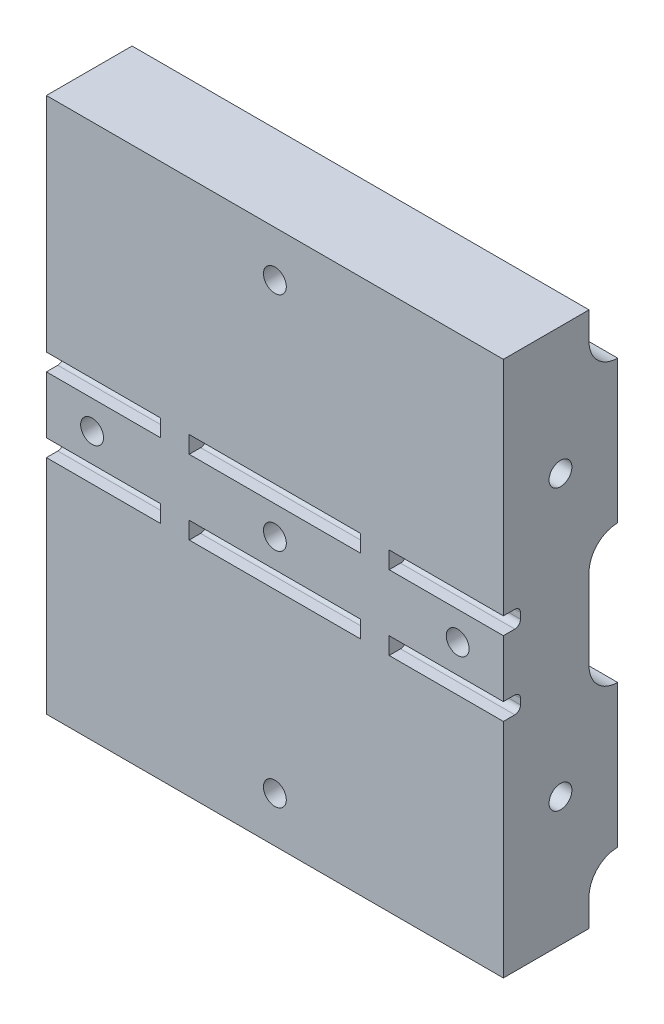
SolidWorks part; units mm, degrees
ref_plane "Front Plane" through (0, 0, 0) normal (0, 0, 1) x (1, 0, 0)
ref_plane "Top Plane" through (0, 0, 0) normal (0, 1, 0) x (1, 0, 0)
ref_plane "Right Plane" through (0, 0, 0) normal (1, 0, 0) x (0, 0, -1)
sketch "Sketch1" plane through (0, 0, 0) normal (0, 0, 1) x (1, 0, 0)
  line L1 (-40, -46.9) -> (40, -46.9)
  line L2 (-40, -46.9) -> (-40, 46.9)
  line L3 (-40, 46.9) -> (40, 46.9)
  line L4 (40, -46.9) -> (40, 46.9)
  line L5 (-40, -46.9) -> (40, 46.9) construction
  line L6 (-40, 46.9) -> (40, -46.9) construction
  point P0 (0, 0)
  dimension "D1" = 80
  dimension "D2" = 93.8
extrude "Boss-Extrude1" add sketch "Sketch1" along normal blind 15
sketch "Sketch2" plane through (0, 0, 0) normal (0, 0, -1) x (-1, 0, 0)
  line L1 (35, -31.9) -> (25, -31.9)
  line L2 (35, -31.9) -> (35, -16.9)
  line L3 (35, -16.9) -> (25, -16.9)
  line L4 (25, -31.9) -> (25, -16.9)
  line L5 (-35, -31.9) -> (-25, -31.9)
  line L6 (-35, -31.9) -> (-35, -16.9)
  line L7 (-35, -16.9) -> (-25, -16.9)
  line L8 (-25, -31.9) -> (-25, -16.9)
  line L9 (35, 17.0849) -> (25, 17.0849)
  line L10 (35, 17.0849) -> (35, 32.0849)
  line L11 (35, 32.0849) -> (25, 32.0849)
  line L12 (25, 17.0849) -> (25, 32.0849)
  line L13 (-25, 17.0849) -> (-35, 17.0849)
  line L14 (-25, 17.0849) -> (-25, 32.0849)
  line L15 (-25, 32.0849) -> (-35, 32.0849)
  line L16 (-35, 17.0849) -> (-35, 32.0849)
extrude "Cut-Extrude1" cut sketch "Sketch2" against normal blind 10
sketch "Sketch3" plane through (40, 0, 0) normal (1, 0, 0) x (0, 0, -1)
  line L0 (-5, 46.9) -> (-5, -46.9) construction
  line L1 (-15, 46.9) -> (0, 46.9) construction
  line L2 (-15, -46.9) -> (0, -46.9) construction
  line L3 (66.1731, 24.5849) -> (-5, 24.5849) construction
  line L4 (66.1731, -24.4) -> (-5, -24.4) construction
  line L5 (0, -46.9) -> (0, 46.9) construction
  circle A0 centre (-5, 24.5849) radius 2
  circle A1 centre (-5, -24.4) radius 2
  dimension "D2" = 4
  dimension "D1" = 5
extrude "Cut-Extrude2" cut sketch "Sketch3" against normal through all
sketch "Sketch4" plane through (0, 0, 0) normal (0, 0, -1) x (-1, 0, 0)
  line L0 (-25, 17.0849) -> (-25, 32.0849) construction
  line L1 (-35, 17.0849) -> (-25, 17.0849) construction
  line L2 (-35, 32.0849) -> (-35, 17.0849) construction
  line L3 (-25, 32.0849) -> (-35, 32.0849) construction
  line L4 (-25, 17.0849) -> (-25, 32.0849)
  line L5 (-35, 17.0849) -> (-25, 17.0849)
  line L6 (-35, 32.0849) -> (-35, 17.0849)
  line L7 (-25, 32.0849) -> (-35, 32.0849)
  line L8 (-20, 12.0849) -> (-20, 37.0849)
  line L9 (-20, 37.0849) -> (-40, 37.0849)
  line L10 (-40, 37.0849) -> (-40, 12.0849)
  line L11 (-40, 12.0849) -> (-20, 12.0849)
  line L12 (0, 46.9) -> (0, 0) construction
  line L13 (-40, 46.9) -> (40, 46.9) construction
  line L14 (0, 0) -> (-40, 0) construction
  line L15 (-40, -46.9) -> (-40, 46.9) construction
  line L16 (25, 32.0849) -> (35, 32.0849)
  line L17 (35, 32.0849) -> (35, 17.0849)
  line L18 (35, 17.0849) -> (25, 17.0849)
  line L19 (25, 17.0849) -> (25, 32.0849)
  line L20 (40, 12.0849) -> (20, 12.0849)
  line L21 (40, 37.0849) -> (40, 12.0849)
  line L22 (20, 37.0849) -> (40, 37.0849)
  line L23 (20, 12.0849) -> (20, 37.0849)
  line L24 (25, -17.0849) -> (25, -32.0849)
  line L25 (35, -17.0849) -> (25, -17.0849)
  line L26 (35, -32.0849) -> (35, -17.0849)
  line L27 (25, -32.0849) -> (35, -32.0849)
  line L28 (20, -12.0849) -> (20, -37.0849)
  line L29 (20, -37.0849) -> (40, -37.0849)
  line L30 (40, -37.0849) -> (40, -12.0849)
  line L31 (40, -12.0849) -> (20, -12.0849)
  line L32 (-25, -32.0849) -> (-35, -32.0849)
  line L33 (-35, -32.0849) -> (-35, -17.0849)
  line L34 (-35, -17.0849) -> (-25, -17.0849)
  line L35 (-25, -17.0849) -> (-25, -32.0849)
  line L36 (-40, -12.0849) -> (-20, -12.0849)
  line L37 (-40, -37.0849) -> (-40, -12.0849)
  line L38 (-20, -37.0849) -> (-40, -37.0849)
  line L39 (-20, -12.0849) -> (-20, -37.0849)
  dimension "D1" = 5
extrude "Boss-Extrude2" add sketch "Sketch4" along normal blind 5
fillet "Fillet1" radius 5 12 edges at (-30, -37.0849, 0) (30, -37.0849, 0) (-30, -12.0849, 0) (30, -12.0849, 0) (-30, 37.0849, 0) (30, 37.0849, 0) (-30, 12.0849, 0) (30, 12.0849, 0) (20, 24.5849, 0) (-20, 24.5849, 0) (-20, -24.5849, 0) (20, -24.5849, 0)
sketch "Sketch5" plane through (0, 0, 0) normal (0, 0, -1) x (-1, 0, 0)
  circle A0 centre (0, -26.9) radius 2
  circle A1 centre (0, 27.08) radius 2
extrude "Cut-Extrude3" cut sketch "Sketch5" against normal blind 2.5
sketch "Sketch6" plane through (40, 0, 0) normal (1, 0, 0) x (0, 0, -1)
  line L0 (-15, -46.9) -> (-15, 46.9) construction
  line L1 (-15, 5) -> (-12, 5)
  line L2 (-15, 5) -> (-15, 8)
  line L3 (-15, 8) -> (-12, 8)
  line L4 (-12, 5) -> (-12, 8)
  line L6 (-15, -5) -> (-12, -5)
  line L7 (-15, -5) -> (-15, -8)
  line L8 (-15, -8) -> (-12, -8)
  line L9 (-12, -5) -> (-12, -8)
  dimension "D1" = 3
  dimension "D2" = 3
  dimension "D3" = 5
  dimension "D4" = 5
extrude "Cut-Extrude4" cut sketch "Sketch6" against normal through all
sketch "Sketch7" plane through (0, 0, 0) normal (0, 0, -1) x (-1, 0, 0)
  line L0 (40, 0) -> (-40, 0) construction
  line L1 (40, 7.0849) -> (40, -7.0849) construction
  line L2 (-40, -7.0849) -> (-40, 7.0849) construction
  line L3 (0, -46.9) -> (0, 46.9) construction
  line L4 (40, -46.9) -> (-40, -46.9) construction
  line L5 (-40, 46.9) -> (40, 46.9) construction
  line L6 (-2.0005, -42.365) -> (-4.001, -38.9)
  line L7 (28.0047, 0) -> (30.0024, -3.46)
  line L8 (30.0024, -3.46) -> (33.9976, -3.46)
  line L9 (33.9976, -3.46) -> (35.9953, 0)
  line L10 (35.9953, 0) -> (33.9976, 3.46)
  line L11 (33.9976, 3.46) -> (30.0024, 3.46)
  line L12 (30.0024, 3.46) -> (28.0047, 0)
  line L13 (-4.001, 38.9) -> (-2.0005, 35.435)
  line L14 (-2.0005, 35.435) -> (2.0005, 35.435)
  line L15 (2.0005, 35.435) -> (4.001, 38.9)
  line L16 (4.001, 38.9) -> (2.0005, 42.365)
  line L17 (2.0005, 42.365) -> (-2.0005, 42.365)
  line L18 (-2.0005, 42.365) -> (-4.001, 38.9)
  line L19 (2.0005, -42.365) -> (-2.0005, -42.365)
  line L20 (4.001, -38.9) -> (2.0005, -42.365)
  line L21 (2.0005, -35.435) -> (4.001, -38.9)
  line L22 (-4.001, -38.9) -> (-2.0005, -35.435)
  line L23 (-30.0024, 3.46) -> (-28.0047, 0)
  line L24 (-33.9976, 3.46) -> (-30.0024, 3.46)
  line L25 (-35.9953, 0) -> (-33.9976, 3.46)
  line L26 (-33.9976, -3.46) -> (-35.9953, 0)
  line L27 (-30.0024, -3.46) -> (-33.9976, -3.46)
  line L28 (-28.0047, 0) -> (-30.0024, -3.46)
  line L29 (2.0005, -35.435) -> (-2.0005, -35.435)
  circle A0 centre (32, 0) radius 3.46 construction
  circle A1 centre (0, 38.9) radius 3.465 construction
  circle A2 centre (0, -38.9) radius 3.465 construction
  circle A3 centre (-32, 0) radius 3.46 construction
  circle A4 centre (32, 0) radius 2
  circle A5 centre (0, 38.9) radius 2
  circle A6 centre (0, -38.9) radius 2
  circle A7 centre (-32, 0) radius 2
  dimension "D3" = 6.93
  dimension "D5" = 4
  dimension "D6" = 4
  dimension "D1" = 6.92
  dimension "D2" = 8
  dimension "D4" = 8
extrude "Cut-Extrude5" cut sketch "Sketch7" against normal blind 3.2
sketch "Sketch8" plane through (0, 0, 0) normal (0, 0, -1) x (-1, 0, 0)
  circle A1 centre (-32, 0) radius 2
  circle A3 centre (-32, 0) radius 2
  circle A4 centre (0, -38.9) radius 2
  circle A6 centre (32, 0) radius 2
  circle A8 centre (0, 38.9) radius 2
  dimension "D1" = 0
extrude "Cut-Extrude6" cut sketch "Sketch8" against normal through all
sketch "Sketch9" plane through (0, 0, -5) normal (0, 0, -1) x (-1, 0, 0)
  line L4 (0, 46.9) -> (0, 0) construction
  line L5 (-40, 46.9) -> (40, 46.9) construction
  line L6 (0, 0) -> (40, 0) construction
  line L7 (40, 7.0849) -> (40, -7.0849) construction
  line L8 (-35.2, 16.8849) -> (-24.8, 16.8849)
  line L9 (-24.8, 16.8849) -> (-24.8, 32.2849)
  line L10 (-24.8, 32.2849) -> (-35.2, 32.2849)
  line L11 (-35.2, 32.2849) -> (-35.2, 16.8849)
  line L12 (-35.2, 16.8849) -> (-24.8, 16.8849)
  line L13 (-24.8, 16.8849) -> (-24.8, 32.2849)
  line L14 (-24.8, 32.2849) -> (-35.2, 32.2849)
  line L15 (-35.2, 32.2849) -> (-35.2, 16.8849)
  line L16 (35.2, 32.2849) -> (35.2, 16.8849)
  line L17 (24.8, 32.2849) -> (35.2, 32.2849)
  line L18 (24.8, 16.8849) -> (24.8, 32.2849)
  line L19 (35.2, 16.8849) -> (24.8, 16.8849)
  line L20 (35.2, -16.8849) -> (24.8, -16.8849)
  line L21 (24.8, -16.8849) -> (24.8, -32.2849)
  line L22 (24.8, -32.2849) -> (35.2, -32.2849)
  line L23 (35.2, -32.2849) -> (35.2, -16.8849)
  line L24 (-35.2, -32.2849) -> (-35.2, -16.8849)
  line L25 (-24.8, -32.2849) -> (-35.2, -32.2849)
  line L26 (-24.8, -16.8849) -> (-24.8, -32.2849)
  line L27 (-35.2, -16.8849) -> (-24.8, -16.8849)
  dimension "D1" = 4.8
extrude "Cut-Extrude7" cut sketch "Sketch9" against normal up to surface (15 mm away) up to face at (30, 24.5849, 10)
sketch "Sketch10" plane through (0, 0, 0) normal (0, 0, -1) x (-1, 0, 0)
  circle A0 centre (0, 0) radius 3.5
  dimension "D1" = 7
extrude "Cut-Extrude8" cut sketch "Sketch10" against normal blind 4
sketch "Sketch11" plane through (0, 0, 0) normal (0, 0, -1) x (-1, 0, 0)
  circle A0 centre (0, 0) radius 2
  dimension "D1" = 4
extrude "Cut-Extrude9" cut sketch "Sketch11" against normal through all
fillet "Fillet3" radius 1 4 edges at (0, -8, 12) (0, -5, 12) (0, 5, 12) (0, 8, 12)
sketch "Sketch12" plane through (0, 0, 15) normal (0, 0, 1) x (1, 0, 0)
  line L0 (0, 0) -> (0, 19.324) construction
  line L1 (-20, 9.9) -> (-15, 9.9)
  line L2 (-20, 9.9) -> (-20, -10.1)
  line L3 (-20, -10.1) -> (-15, -10.1)
  line L4 (-15, 9.9) -> (-15, -10.1)
  line L5 (-40, 46.9) -> (-40, 8) construction
  line L6 (40, 46.9) -> (-40, 46.9) construction
  line L7 (15, 9.9) -> (15, -10.1)
  line L8 (20, -10.1) -> (15, -10.1)
  line L9 (20, 9.9) -> (20, -10.1)
  line L10 (20, 9.9) -> (15, 9.9)
  dimension "D1" = 20
  dimension "D2" = 5
  dimension "D3" = 20
  dimension "D4" = 37
extrude "Boss-Extrude4" add sketch "Sketch12" against normal blind 5
